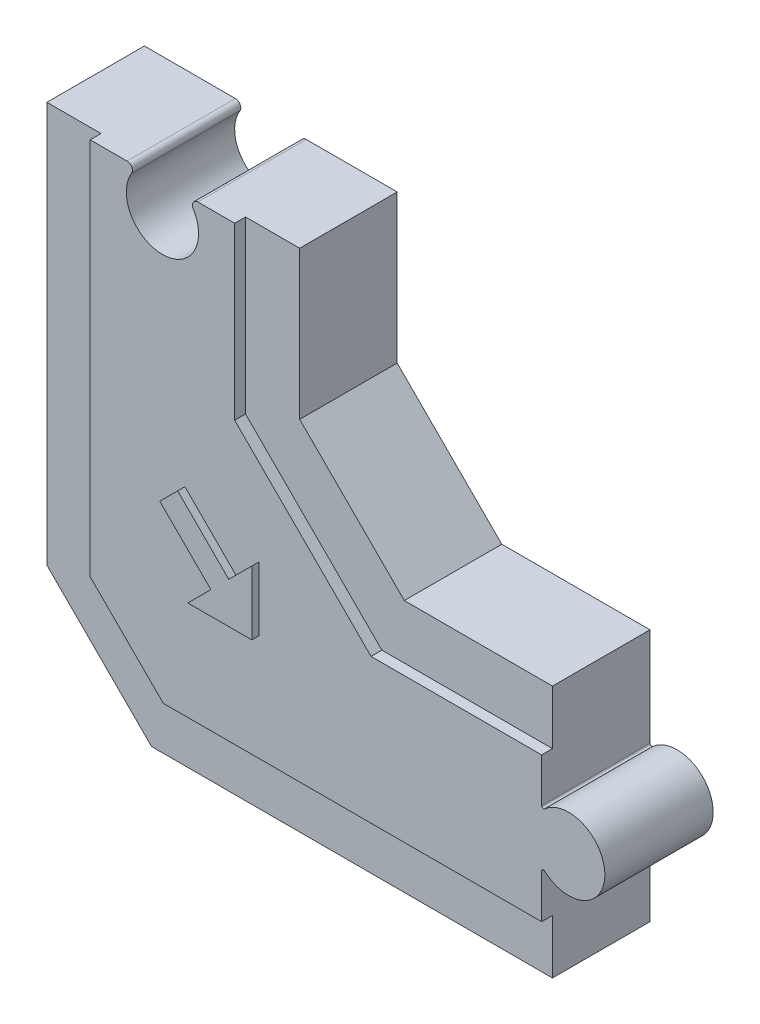
SolidWorks part; units mm, degrees
ref_plane "Face" through (0, 0, 0) normal (0, 0, 1) x (1, 0, 0)
ref_plane "Dessus" through (0, 0, 0) normal (0, 1, 0) x (1, 0, 0)
ref_plane "Droite" through (0, 0, 0) normal (1, 0, 0) x (0, 0, -1)
sketch "Esquisse1" plane through (0, 0, 0) normal (0, 0, 1) x (1, 0, 0)
  line L0 (0, 0) -> (0, 85.9091) construction
  line L1 (0, 0) -> (106.8028, 0) construction
  line L2 (-35, 105) -> (35, 105)
  line L3 (35, 105) -> (35, 35)
  line L4 (35, 35) -> (105, 35)
  line L5 (105, 35) -> (105, -35)
  line L6 (105, -35) -> (-35, -35)
  line L7 (-35, -35) -> (-35, 105)
  dimension "D1" = 140
  dimension "D2" = 70
extrude "Boss.-Extru.1" add sketch "Esquisse1" along normal blind 30
sketch "Esquisse2" plane through (0, 0, 30) normal (0, 0, 1) x (1, 0, 0)
  line L0 (-35, 105) -> (-35, -35) construction
  line L1 (-35, -35) -> (105, -35) construction
  line L2 (35, 63.9694) -> (63.9694, 35)
  line L3 (35, 35) -> (35, 105) construction
  line L4 (105, 35) -> (35, 35) construction
  line L5 (63.9694, 35) -> (35, 35)
  line L6 (35, 35) -> (35, 63.9694)
  circle A0 centre (14.49, 14.49) radius 49.49 construction
  dimension "D1" = 98.98
  dimension "D2" = 45
extrude "Boss.-Extru.2" add sketch "Esquisse2" against normal up to surface (30 mm away) up to face at (35, 35, 0)
sketch "Esquisse3" plane through (0, 0, 30) normal (0, 0, 1) x (1, 0, 0)
  line L0 (-35, -35) -> (105, -35) construction
  line L1 (-35, 105) -> (-35, -35) construction
  line L2 (-35, -35) -> (-6.0094, -35)
  line L3 (-35, -6.0094) -> (-35, -35)
  line L4 (-35, -6.0094) -> (-6.0094, -35)
  line L5 (35, 63.9694) -> (63.9694, 35) construction
  circle A0 centre (14.49, 14.49) radius 49.49 construction
extrude "Enlèv. mat.-Extru.1" cut sketch "Esquisse3" against normal through all
sketch "Esquisse4" plane through (0, 0, 30) normal (0, 0, 1) x (1, 0, 0)
  line L0 (35, 105) -> (-35, 105) construction
  circle A0 centre (0, 97.5) radius 10
  dimension "D1" = 20
  dimension "D2" = 7.5
extrude "Enlèv. mat.-Extru.2" cut sketch "Esquisse4" against normal blind 50
sketch "Esquisse5" plane through (0, 0, 30) normal (0, 0, 1) x (1, 0, 0)
  line L0 (105, -35) -> (105, 35) construction
  circle A0 centre (112.5, 0) radius 10
  dimension "D1" = 20
  dimension "D2" = 7.5
extrude "Boss.-Extru.3" add sketch "Esquisse5" against normal through all
sketch "Esquisse7" plane through (0, 0, 30) normal (0, 0, 1) x (1, 0, 0)
  line L257 (20, 57.7562) -> (20, 105)
  line L258 (57.7562, 20) -> (20, 57.7562)
  line L259 (105, 20) -> (57.7562, 20)
  line L260 (20, 57.7562) -> (20, 105)
  line L261 (57.7562, 20) -> (20, 57.7562)
  line L262 (105, 20) -> (57.7562, 20)
  line L266 (0.2038, -20) -> (105, -20)
  line L267 (-20, 0.2038) -> (0.2038, -20)
  line L268 (-20, 105) -> (-20, 0.2038)
  line L269 (0.2038, -20) -> (105, -20)
  line L270 (-20, 0.2038) -> (0.2038, -20)
  line L271 (-20, 105) -> (-20, 0.2038)
  line L279 (105, -35) -> (105, -6.6144)
  line L280 (105, 6.6144) -> (105, 35)
  line L281 (105, 35) -> (63.9694, 35)
  line L282 (63.9694, 35) -> (35, 63.9694)
  line L283 (35, 63.9694) -> (35, 105)
  line L284 (35, 105) -> (6.6144, 105)
  line L285 (-6.6144, 105) -> (-35, 105)
  line L286 (-35, 105) -> (-35, -6.0094)
  line L287 (-35, -6.0094) -> (-6.0094, -35)
  line L288 (-6.0094, -35) -> (105, -35)
  line L289 (105, -35) -> (105, -20)
  line L290 (105, 20) -> (105, 35)
  line L291 (105, 35) -> (63.9694, 35)
  line L292 (63.9694, 35) -> (35, 63.9694)
  line L293 (35, 63.9694) -> (35, 105)
  line L294 (35, 105) -> (20, 105)
  line L295 (-20, 105) -> (-35, 105)
  line L296 (-35, 105) -> (-35, -6.0094)
  line L297 (-35, -6.0094) -> (-6.0094, -35)
  line L298 (-6.0094, -35) -> (105, -35)
  arc A2 (105, -6.6144) -> (105, 6.6144) centre (112.5, 0) ccw
  arc A3 (-6.6144, 105) -> (6.6144, 105) centre (0, 97.5) ccw
  dimension "D1" = 15
  dimension "D2" = 15
  dimension "D3" = 0
extrude "Enlèv. mat.-Extru.3" cut sketch "Esquisse7" against normal blind 3
sketch "Esquisse8" plane through (0, 0, 30) normal (0, 0, 1) x (1, 0, 0)
  line L0 (1.2671, 29.9769) -> (6.2168, 34.9266)
  line L1 (6.2168, 34.9266) -> (20.3589, 20.7845)
  line L2 (1.2671, 29.9769) -> (15.4092, 15.8347)
  line L3 (15.4092, 15.8347) -> (9.0319, 9.4574)
  line L4 (9.0319, 9.4574) -> (26.7363, 9.4574)
  line L5 (26.7363, 9.4574) -> (26.7363, 27.1618)
  line L6 (26.7363, 27.1618) -> (20.3589, 20.7845)
  line L7 (3.7419, 32.4518) -> (26.7363, 9.4574) construction
  dimension "D1" = 20
  dimension "D2" = 7
extrude "Boss.-Extru.4" add sketch "Esquisse8" along normal blind 2
fillet "Congé2" radius 0.5 2 edges at (105, 6.6144, 15) (105, -6.6144, 15)
fillet "Congé3" radius 1.5 2 edges at (6.6144, 105, 15) (-6.6144, 105, 15)
shell "Coque1" thickness 3 removed face at (44.1282, 41.8079, 0)
